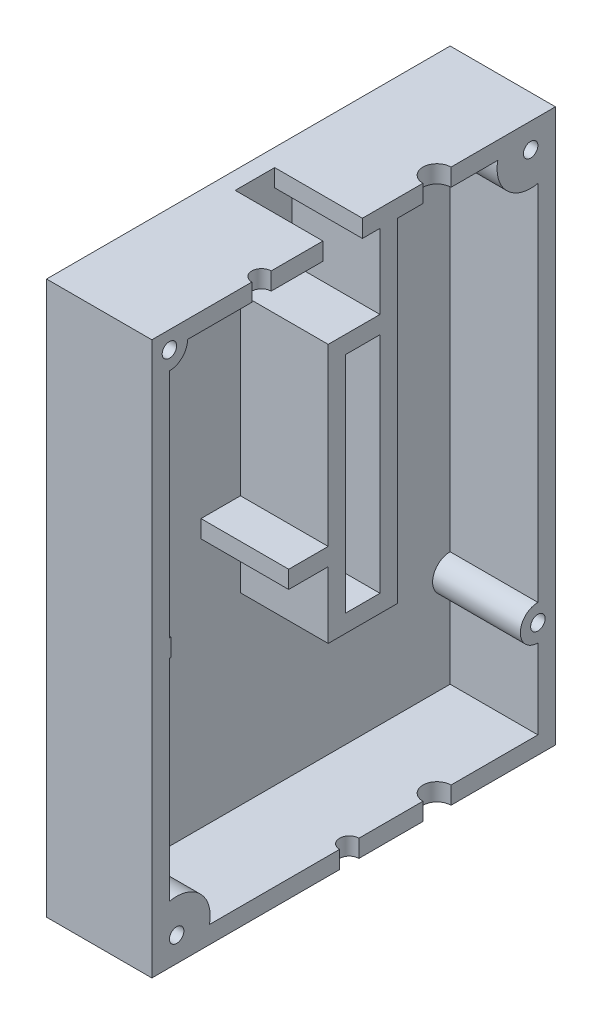
SolidWorks part; units mm, degrees
ref_plane "前视基准面" through (0, 0, 0) normal (0, 0, 1) x (1, 0, 0)
ref_plane "上视基准面" through (0, 0, 0) normal (0, 1, 0) x (1, 0, 0)
ref_plane "右视基准面" through (0, 0, 0) normal (1, 0, 0) x (0, 0, -1)
other "Configuration Table"
sketch "草图1" plane through (0, 0, 0) normal (1, 0, 0) x (0, 0, -1)
  line L1 (-23, 31.5) -> (23, 31.5)
  line L2 (-23, 31.5) -> (-23, -31.5)
  line L3 (-23, -31.5) -> (23, -31.5)
  line L4 (23, 31.5) -> (23, -31.5)
  line L5 (-23, 31.5) -> (23, -31.5) construction
  line L6 (-23, -31.5) -> (23, 31.5) construction
  point P0 (0, 0)
  dimension "D1" = 63
  dimension "D2" = 46
extrude "凸台-拉伸1" add sketch "草图1" along normal blind 12
shell "抽壳1" thickness 2 removed face at (12, 0, 0)
sketch "草图3" plane through (2, 0, 0) normal (1, 0, 0) x (0, 0, -1)
  line L19 (-2.9, 21) -> (3, 21)
  line L20 (-2.9, 21) -> (-2.9, 1.0513)
  line L21 (-2.9, -8.525) -> (5, -8.525)
  line L22 (5, 17.175) -> (5, -8.525)
  line L24 (3.5, -8.725) -> (-4.5, -8.725) construction
  line L25 (8, 24.825) -> (8, -27.175) construction
  line L26 (21, 29.5) -> (-21, 29.5) construction
  line L27 (-21, 29.5) -> (-21, -29.5) construction
  line L28 (3, 29.5) -> (5, 29.5)
  line L29 (3, 29.5) -> (3, 21)
  line L31 (5, 29.5) -> (5, 17.175)
  line L32 (-0.9, 19) -> (3, 19)
  line L33 (-0.9, 19) -> (-0.9, -6.525)
  line L34 (-0.9, -6.525) -> (3, -6.525)
  line L35 (3, 19) -> (3, -6.525)
  line L36 (-21, 1.0513) -> (-20.8, 1.0513)
  line L37 (-21, 1.0513) -> (-21, -0.9487)
  line L38 (-21, -0.9487) -> (-20.8, -0.9487)
  line L39 (-20.8, 1.0513) -> (-20.8, -0.9487)
  line L41 (-7.4, 1.0513) -> (-2.9, 1.0513)
  line L42 (-7.4, 1.0513) -> (-7.4, -0.9487)
  line L43 (-7.4, -0.9487) -> (-2.9, -0.9487)
  line L48 (-2.9, -0.9487) -> (-2.9, -8.525)
  dimension "D2" = 0.2
  dimension "D3" = 3
  dimension "D4" = 8.5
  dimension "D5" = 2
  dimension "D6" = 2
  dimension "D7" = 2
  dimension "D8" = 2
  dimension "D9" = 2
  dimension "D10" = 0.2
  dimension "D13" = 2
  dimension "D14" = 2
extrude "凸台-拉伸6" add sketch "草图3" along normal up to surface (10 mm away) up to face at (12, 0, 0)
sketch "草图4" plane through (0, 31.5, 0) normal (0, 1, 0) x (1, 0, 0)
  line L0 (2, 3) -> (2, -21) construction
  line L1 (12, 1) -> (2, 1)
  line L2 (12, 1) -> (12, -3.5)
  line L3 (12, -3.5) -> (2, -3.5)
  line L4 (2, 1) -> (2, -3.5)
  line L5 (12, -3.5) -> (22, -3.5) construction
  circle A1 centre (12, -10.5) radius 1.1
  circle A2 centre (12, 9.5) radius 1.6
  arc A3 (12, 7.9) -> (12, 11.1) centre (12, 9.5) ccw construction
  arc A4 (12, -11.6) -> (12, -9.4) centre (12, -10.5) ccw construction
extrude "切除-拉伸1" cut sketch "草图4" against normal up to next
sketch "草图5" plane through (0, -31.5, 0) normal (0, -1, 0) x (1, 0, 0)
  circle A0 centre (12, -9.5) radius 1.6
  circle A1 centre (12, 0.5) radius 1.1
  circle A2 centre (12, 0.5) radius 1 construction
  arc A3 (12, -7.9) -> (12, -11.1) centre (12, -9.5) ccw construction
  dimension "D1" = 0.1
extrude "切除-拉伸2" cut sketch "草图5" against normal blind 19.3
sketch "草图6" plane through (2, 0, 0) normal (1, 0, 0) x (0, 0, -1)
  line L0 (21, -29.5) -> (21, 29.5) construction
  line L1 (21, 29.5) -> (11.1, 29.5) construction
  line L2 (16.7315, -20.925) -> (15.49, -20.925) construction
  line L3 (23, -31.5) -> (23, 31.5) construction
  line L4 (-23, -26.0962) -> (-23, -31.5)
  line L5 (-21, -29.5) -> (-1.6, -29.5) construction
  line L6 (-23, -31.5) -> (-17.5962, -31.5)
  line L7 (-21, -0.9487) -> (-21, -29.5) construction
  line L11 (-23, 28.9472) -> (-23, 30.0528)
  line L12 (-21.5528, 31.5) -> (-20.4472, 31.5)
  line L14 (-23, -31.5) -> (-1.6, -31.5) construction
  line L15 (-23, 31.5) -> (-23, -31.5) construction
  line L16 (-11.6, 31.5) -> (-23, 31.5) construction
  line L18 (17.5962, 31.5) -> (23, 31.5)
  line L19 (23, 31.5) -> (23, 26.0962)
  circle A0 centre (-20.175, -28.675) radius 0.825
  circle A1 centre (20.175, 28.675) radius 0.825
  circle A2 centre (21, -18.425) radius 0.825
  circle A3 centre (-21, 29.5) radius 0.825
  circle A5 centre (21, -18.425) radius 2
  arc A7 (-23, 28.9472) -> (-20.4472, 31.5) centre (-21, 29.5) ccw
  arc A8 (-21.5528, 31.5) -> (-23, 30.0528) centre (-21, 29.5) ccw
  arc A10 (-17.5962, -31.5) -> (-23, -26.0962) centre (-20.175, -28.675) ccw
  arc A11 (17.5962, 31.5) -> (23, 26.0962) centre (20.175, 28.675) ccw
  dimension "D1" = 1.65
  dimension "D2" = 1.65
  dimension "D3" = 1.65
  dimension "D4" = 1.65
  dimension "D6" = 3
  dimension "D7" = 3
  dimension "D8" = 1.25
  dimension "D5" = 2.5
extrude "凸台-拉伸7" add sketch "草图6" along normal up to surface (10 mm away) up to face at (12, 0.0171, 16.5)
sketch "草图7" plane through (12, 0, 0) normal (1, 0, 0) x (0, 0, -1)
  line L0 (21, -19.25) -> (21, -17.6) construction
  circle A1 centre (21, -18.425) radius 0.825
  circle A3 centre (-21, 29.5) radius 0.825
  arc A5 (21, -17.6) -> (21, -19.25) centre (21, -18.425) ccw construction
  arc A7 (-21, 28.675) -> (-20.175, 29.5) centre (-21, 29.5) ccw construction
extrude "切除-拉伸3" cut sketch "草图7" against normal blind 2.5
sketch "草图8" plane through (2, 0, 0) normal (1, 0, 0) x (0, 0, -1)
  line L0 (-23, 31.5) -> (-18.925, 31.5)
  line L1 (-11.6, 31.5) -> (-23, 31.5) construction
  line L2 (-18.925, 31.5) -> (-18.925, 29.5)
  line L3 (-21, 27.425) -> (-23, 27.425)
  line L4 (-23, 31.5) -> (-23, -31.5) construction
  line L5 (-23, 27.425) -> (-23, 31.5)
  line L6 (21, -19.25) -> (21, -17.6) construction
  line L7 (22, -16.6929) -> (22, -20.1571)
  line L8 (23, -31.5) -> (23, 31.5) construction
  arc A0 (-21, 27.425) -> (-18.925, 29.5) centre (-21, 29.5) ccw construction
  arc A1 (-21, 27.425) -> (-18.925, 29.5) centre (-21, 29.5) ccw
  arc A2 (22, -16.6929) -> (22, -20.1571) centre (21, -18.425) ccw
  arc A3 (21, -16.425) -> (21, -20.425) centre (21, -18.425) ccw construction
  dimension "D1" = 1
extrude "凸台-拉伸8" add sketch "草图8" along normal up to surface (7.5 mm away) from surface up to face at (9.5, 29.557, 21.057) starting at face at (2, 7.278, 2.8702)
